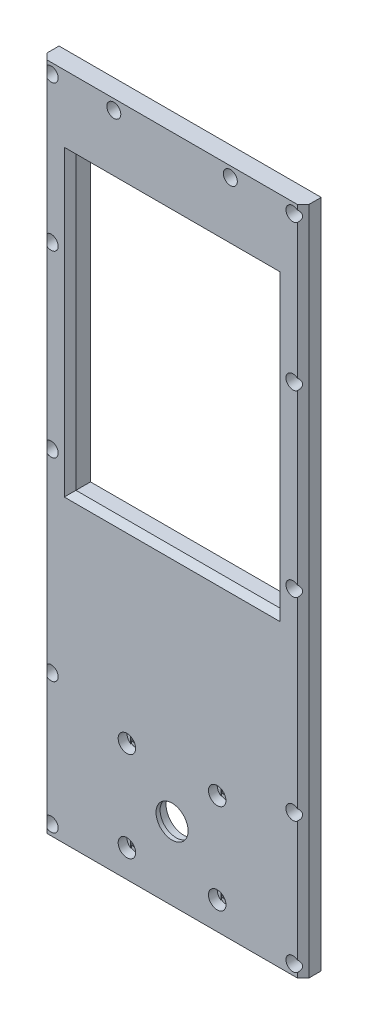
SolidWorks part; units mm, degrees
ref_plane "Front Plane" through (0, 0, 0) normal (0, 0, 1) x (1, 0, 0)
ref_plane "Top Plane" through (0, 0, 0) normal (0, 1, 0) x (1, 0, 0)
ref_plane "Right Plane" through (0, 0, 0) normal (1, 0, 0) x (0, 0, -1)
sketch "Sketch1" plane through (0, 0, 0) normal (0, 0, 1) x (1, 0, 0)
  line L1 (-45, -115) -> (45, -115)
  line L2 (-45, -115) -> (-45, 115)
  line L3 (-45, 115) -> (45, 115)
  line L4 (45, -115) -> (45, 115)
  line L5 (-45, -115) -> (45, 115) construction
  line L6 (-45, 115) -> (45, -115) construction
  line L7 (-38, -108) -> (38, -108)
  line L8 (-38, -108) -> (-38, 108)
  line L9 (-38, 108) -> (38, 108)
  line L10 (38, -108) -> (38, 108)
  line L11 (-38, -108) -> (38, 108) construction
  line L12 (-38, 108) -> (38, -108) construction
  point P0 (0, 0)
  point P6 (0, 0)
  dimension "D1" = 230
  dimension "D2" = 90
  dimension "D3" = 7
  dimension "D4" = 7
extrude "Boss-Extrude1" add sketch "Sketch1" along normal blind 7
sketch "Sketch2" plane through (0, 0, 7) normal (0, 0, 1) x (1, 0, 0)
  line L0 (38, -108) -> (38, 108) construction
  line L1 (-38, -108) -> (38, -108)
  line L2 (-38, -108) -> (-38, -58)
  line L3 (-38, -58) -> (38, -58)
  line L4 (38, -108) -> (38, -58)
  dimension "D1" = 50
extrude "Boss-Extrude2" add sketch "Sketch2" against normal up to surface (7 mm away) up to face at (0, 0, 0)
sketch "Sketch3" plane through (0, 0, 0) normal (0, 0, -1) x (-1, 0, 0)
  line L0 (0, -115) -> (0, -90) construction
  line L1 (45, -115) -> (-45, -115) construction
  circle A0 centre (0, -90) radius 5.5
  dimension "D1" = 11
  dimension "D2" = 25
extrude "Cut-Extrude1" cut sketch "Sketch3" against normal through all
sketch "Sketch4" plane through (0, 0, 0) normal (0, 0, -1) x (-1, 0, 0)
  circle A0 centre (0, -90) radius 6.05
  dimension "D1" = 12.1
extrude "Cut-Extrude2" cut sketch "Sketch4" against normal offset from surface (5.6 mm away) 1.4 up to face at (-5.5, -90, 7)
sketch "Sketch5" plane through (0, 0, 0) normal (0, 0, -1) x (-1, 0, 0)
  circle A0 centre (0, -90) radius 12
  dimension "D1" = 24
extrude "Cut-Extrude3" cut sketch "Sketch5" against normal offset from surface (3 mm away) 2.6 up to face at (-6.05, -90, 5.6)
sketch "Sketch6" plane through (0, 0, 0) normal (0, 0, -1) x (-1, 0, 0)
  line L1 (-15.5, -105.5) -> (15.5, -105.5) construction
  line L2 (-15.5, -105.5) -> (-15.5, -74.5) construction
  line L3 (-15.5, -74.5) -> (15.5, -74.5) construction
  line L4 (15.5, -105.5) -> (15.5, -74.5) construction
  line L5 (-15.5, -105.5) -> (15.5, -74.5) construction
  line L6 (-15.5, -74.5) -> (15.5, -105.5) construction
  circle A0 centre (-15.5, -74.5) radius 1.7
  circle A1 centre (15.5, -74.5) radius 1.7
  circle A2 centre (15.5, -105.5) radius 1.7
  circle A3 centre (-15.5, -105.5) radius 1.7
  point P0 (0, -90)
  dimension "D2" = 3.4
  dimension "D1" = 31
extrude "Cut-Extrude4" cut sketch "Sketch6" against normal through all
sketch "Sketch7" plane through (0, 0, 0) normal (0, 0, -1) x (-1, 0, 0)
  line L1 (-30, -112.5) -> (30, -112.5)
  line L2 (-30, -112.5) -> (-30, -67.5)
  line L3 (-30, -67.5) -> (30, -67.5)
  line L4 (30, -112.5) -> (30, -67.5)
  line L5 (-30, -112.5) -> (30, -67.5) construction
  line L6 (-30, -67.5) -> (30, -112.5) construction
  point P0 (0, -90)
  dimension "D1" = 60
  dimension "D2" = 45
extrude "Cut-Extrude5" cut sketch "Sketch7" against normal blind 1
sketch "Sketch8" plane through (0, 0, 7) normal (0, 0, 1) x (1, 0, 0)
  circle A0 centre (-15.5, -74.5) radius 3
  circle A1 centre (15.5, -74.5) radius 3
  circle A2 centre (15.5, -105.5) radius 3
  circle A3 centre (-15.5, -105.5) radius 3
  dimension "D1" = 6
extrude "Cut-Extrude6" cut sketch "Sketch8" against normal blind 3
sketch "Sketch9" plane through (0, 0, 7) normal (0, 0, 1) x (1, 0, 0)
  line L0 (-45, 115) -> (-45, -115) construction
  line L1 (-41.5, -111.5) -> (41.5, -111.5) construction
  line L2 (-41.5, -111.5) -> (-41.5, 111.5) construction
  line L3 (-41.5, 111.5) -> (41.5, 111.5) construction
  line L4 (41.5, -111.5) -> (41.5, 111.5) construction
  line L5 (-41.5, -111.5) -> (41.5, 111.5) construction
  line L6 (-41.5, 111.5) -> (41.5, -111.5) construction
  line L7 (45, 115) -> (-45, 115) construction
  circle A0 centre (-41.5, 111.5) radius 1.45
  circle A1 centre (41.5, 111.5) radius 1.45
  circle A4 centre (-41.5, -111.5) radius 1.45
  circle A5 centre (41.5, -111.5) radius 1.45
  circle A6 centre (-41.5, 61.5) radius 1.45
  circle A7 centre (41.5, 61.5) radius 1.45
  circle A8 centre (41.5, -66.5) radius 1.45
  circle A9 centre (-41.5, -66.5) radius 1.45
  circle A10 centre (-41.5, 0) radius 1.45
  circle A11 centre (41.5, 0) radius 1.45
  point P0 (0, 0)
  dimension "D3" = 2.9
  dimension "D1" = 3.5
  dimension "D2" = 3.5
  dimension "D4" = 45
  dimension "D5" = 50
extrude "Cut-Extrude7" cut sketch "Sketch9" against normal through all
sketch "Sketch10" plane through (0, 0, 7) normal (0, 0, 1) x (1, 0, 0)
  circle A0 centre (-41.5, 111.5) radius 2.4
  circle A1 centre (41.5, 61.5) radius 2.4
  circle A2 centre (-41.5, 61.5) radius 2.4
  circle A3 centre (41.5, 111.5) radius 2.4
  circle A4 centre (-41.5, -111.5) radius 2.4
  circle A5 centre (41.5, -111.5) radius 2.4
  circle A6 centre (-41.5, -66.5) radius 2.4
  circle A7 centre (41.5, -66.5) radius 2.4
  circle A8 centre (-41.5, 0) radius 2.4
  circle A9 centre (41.5, 0) radius 2.4
  dimension "D1" = 4.8
extrude "Cut-Extrude8" cut sketch "Sketch10" against normal blind 5
chamfer "Chamfer1" distance 2 angle 45 2 edges at (-45, 0, 7) (45, 0, 7)
sketch "Sketch11" plane through (0, 0, 7) normal (0, 0, 1) x (1, 0, 0)
  line L0 (38, -58) -> (38, 108) construction
  line L1 (-38, -58) -> (38, -58)
  line L2 (-38, -58) -> (-38, -36.4)
  line L3 (-38, -36.4) -> (38, -36.4)
  line L4 (38, -58) -> (38, -36.4)
  line L5 (-43, -115) -> (43, -115) construction
  dimension "D1" = 78.6
extrude "Boss-Extrude3" add sketch "Sketch11" against normal up to surface (7 mm away) up to face at (-40.05, 0, 0)
sketch "Sketch12" plane through (0, 0, 7) normal (0, 0, 1) x (1, 0, 0)
  line L0 (-41.5, 111.5) -> (41.5, 111.5) construction
  line L1 (-20, 111.5) -> (20, 111.5) construction
  circle A0 centre (-20, 111.5) radius 1.45
  circle A1 centre (20, 111.5) radius 1.45
  circle A2 centre (-41.5, 111.5) radius 1.45 construction
  point P7 (0, 111.5)
  dimension "D1" = 40
extrude "Cut-Extrude9" cut sketch "Sketch12" against normal through all
sketch "Sketch13" plane through (0, 0, 7) normal (0, 0, 1) x (1, 0, 0)
  circle A0 centre (-20, 111.5) radius 2.4
  circle A1 centre (20, 111.5) radius 2.4
  circle A2 centre (-41.5, 111.5) radius 2.4 construction
extrude "Cut-Extrude10" cut sketch "Sketch13" against normal up to surface (5 mm away) up to face at (-39.1, 111.5, 2)
chamfer "Chamfer2" distance 0.8 angle 45 12 edges at (0, -115, 0) (-45, 0, 0) (0, 115, 0) (45, 0, 0) (38, 35.8, 7) (0, 108, 7) (-38, 35.8, 7) (0, -36.4, 7) (-38, 35.8, 0) (0, 108, 0) (38, 35.8, 0) (0, -36.4, 0)
sketch "Sketch14" plane through (0, 0, 2) normal (0, 0, 1) x (1, 0, 0)
  line L2 (-42.95, -68.4125) -> (-42.95, -64.5875)
  line L4 (-40.05, -68.4125) -> (-40.05, -64.5875)
  line L5 (-42.95, -68.4125) -> (-40.05, -64.5875) construction
  line L6 (-42.95, -64.5875) -> (-40.05, -68.4125) construction
  line L14 (-42.95, -113.4125) -> (-42.95, -109.5875)
  line L16 (-40.05, -113.4125) -> (-40.05, -109.5875)
  line L17 (-42.95, -113.4125) -> (-40.05, -109.5875) construction
  line L18 (-42.95, -109.5875) -> (-40.05, -113.4125) construction
  line L26 (-42.95, 59.5875) -> (-42.95, 63.4125)
  line L28 (-40.05, 59.5875) -> (-40.05, 63.4125)
  line L29 (-42.95, 59.5875) -> (-40.05, 63.4125) construction
  line L30 (-42.95, 63.4125) -> (-40.05, 59.5875) construction
  line L32 (-21.45, 109.5875) -> (-21.45, 113.4125)
  line L34 (-18.55, 109.5875) -> (-18.55, 113.4125)
  line L35 (-21.45, 109.5875) -> (-18.55, 113.4125) construction
  line L36 (-21.45, 113.4125) -> (-18.55, 109.5875) construction
  line L38 (-42.95, 109.5875) -> (-42.95, 113.4125)
  line L40 (-40.05, 109.5875) -> (-40.05, 113.4125)
  line L41 (-42.95, 109.5875) -> (-40.05, 113.4125) construction
  line L42 (-42.95, 113.4125) -> (-40.05, 109.5875) construction
  arc A0 (-43, -68.3735) -> (-43, -64.6265) centre (-41.5, -66.5) ccw construction
  circle A2 centre (-41.5, -111.5) radius 2.4 construction
  circle A4 centre (-41.5, 61.5) radius 2.4 construction
  circle A5 centre (-20, 111.5) radius 2.4 construction
  circle A6 centre (-41.5, 111.5) radius 2.4 construction
  circle A7 centre (-41.5, 111.5) radius 1.45 construction
  circle A8 centre (-20, 111.5) radius 1.45 construction
  circle A9 centre (-41.5, 61.5) radius 1.45 construction
  circle A10 centre (-41.5, -66.5) radius 1.45 construction
  circle A12 centre (-41.5, -111.5) radius 1.45 construction
  arc A16 (-21.45, 109.5875) -> (-18.55, 109.5875) centre (-20, 111.5) ccw
  arc A17 (-40.05, 113.4125) -> (-42.95, 113.4125) centre (-41.5, 111.5) ccw
  arc A18 (-40.05, 63.4125) -> (-42.95, 63.4125) centre (-41.5, 61.5) ccw
  arc A20 (-42.95, -68.4125) -> (-40.05, -68.4125) centre (-41.5, -66.5) ccw
  arc A22 (-40.05, -109.5875) -> (-42.95, -109.5875) centre (-41.5, -111.5) ccw
  arc A23 (-42.95, 109.5875) -> (-40.05, 109.5875) centre (-41.5, 111.5) ccw
  arc A24 (-18.55, 113.4125) -> (-21.45, 113.4125) centre (-20, 111.5) ccw
  arc A25 (-42.95, 59.5875) -> (-40.05, 59.5875) centre (-41.5, 61.5) ccw
  arc A26 (-40.05, -64.5875) -> (-42.95, -64.5875) centre (-41.5, -66.5) ccw
  arc A29 (-42.95, -113.4125) -> (-40.05, -113.4125) centre (-41.5, -111.5) ccw
  point P0 (-41.5, -66.5)
  point P17 (-41.5, -111.5)
  point P33 (-41.5, 61.5)
  point P41 (-20, 111.5)
  point P49 (-41.5, 111.5)
extrude "Cut-Extrude11" cut sketch "Sketch14" against normal blind 0.2
sketch "Sketch15" plane through (0, 0, 1.8) normal (0, 0, 1) x (1, 0, 0)
  line L0 (-40.05, -111.5) -> (-40.05, -109.5875) construction
  line L1 (-42.95, -112.95) -> (-40.05, -112.95)
  line L2 (-42.95, -112.95) -> (-42.95, -110.05)
  line L3 (-42.95, -110.05) -> (-40.05, -110.05)
  line L4 (-40.05, -112.95) -> (-40.05, -110.05)
  line L5 (-42.95, -112.95) -> (-40.05, -110.05) construction
  line L6 (-42.95, -110.05) -> (-40.05, -112.95) construction
  line L7 (-40.05, 61.5) -> (-40.05, 63.4125) construction
  line L8 (-42.95, -67.95) -> (-40.05, -67.95)
  line L9 (-42.95, -67.95) -> (-42.95, -65.05)
  line L10 (-42.95, -65.05) -> (-40.05, -65.05)
  line L11 (-40.05, -67.95) -> (-40.05, -65.05)
  line L12 (-42.95, -67.95) -> (-40.05, -65.05) construction
  line L13 (-42.95, -65.05) -> (-40.05, -67.95) construction
  line L14 (-42.95, 60.05) -> (-40.05, 60.05)
  line L15 (-42.95, 60.05) -> (-42.95, 62.95)
  line L16 (-42.95, 62.95) -> (-40.05, 62.95)
  line L17 (-40.05, 60.05) -> (-40.05, 62.95)
  line L18 (-42.95, 60.05) -> (-40.05, 62.95) construction
  line L19 (-42.95, 62.95) -> (-40.05, 60.05) construction
  line L20 (-40.05, 109.5875) -> (-40.05, 113.4125) construction
  line L21 (-42.95, 110.05) -> (-40.05, 110.05)
  line L22 (-42.95, 110.05) -> (-42.95, 112.95)
  line L23 (-42.95, 112.95) -> (-40.05, 112.95)
  line L24 (-40.05, 110.05) -> (-40.05, 112.95)
  line L25 (-42.95, 110.05) -> (-40.05, 112.95) construction
  line L26 (-42.95, 112.95) -> (-40.05, 110.05) construction
  line L27 (-18.55, 109.5875) -> (-18.55, 113.4125) construction
  line L28 (-21.45, 110.05) -> (-18.55, 110.05)
  line L29 (-21.45, 110.05) -> (-21.45, 112.95)
  line L30 (-21.45, 112.95) -> (-18.55, 112.95)
  line L31 (-18.55, 110.05) -> (-18.55, 112.95)
  line L32 (-21.45, 110.05) -> (-18.55, 112.95) construction
  line L33 (-21.45, 112.95) -> (-18.55, 110.05) construction
  arc A0 (-40.05, -66.5) -> (-42.95, -66.5) centre (-41.5, -66.5) ccw construction
  arc A1 (-40.05, 61.5) -> (-42.95, 61.5) centre (-41.5, 61.5) ccw construction
  arc A2 (-18.55, 111.5) -> (-21.45, 111.5) centre (-20, 111.5) ccw construction
  arc A3 (-40.05, 111.5) -> (-42.95, 111.5) centre (-41.5, 111.5) ccw construction
  point P0 (-41.5, -111.5)
  point P8 (-41.5, -66.5)
  point P17 (-41.5, 61.5)
  point P28 (-41.5, 111.5)
  point P36 (-20, 111.5)
extrude "Cut-Extrude12" cut sketch "Sketch15" against normal blind 0.2
sketch "Sketch16" plane through (0, 0, 4) normal (0, 0, 1) x (1, 0, 0)
  line L2 (-17.2, -76.9718) -> (-17.2, -72.0282)
  line L4 (-13.8, -76.9718) -> (-13.8, -72.0282)
  line L5 (-17.2, -76.9718) -> (-13.8, -72.0282) construction
  line L6 (-17.2, -72.0282) -> (-13.8, -76.9718) construction
  line L8 (-17.2, -107.9718) -> (-17.2, -103.0282)
  line L10 (-13.8, -107.9718) -> (-13.8, -103.0282)
  line L11 (-17.2, -107.9718) -> (-13.8, -103.0282) construction
  line L12 (-17.2, -103.0282) -> (-13.8, -107.9718) construction
  circle A0 centre (-15.5, -74.5) radius 3 construction
  circle A1 centre (-15.5, -105.5) radius 3 construction
  circle A2 centre (-15.5, -105.5) radius 1.7 construction
  circle A3 centre (-15.5, -74.5) radius 1.7 construction
  circle A4 centre (-15.5, -105.5) radius 3 construction
  circle A5 centre (-15.5, -74.5) radius 3 construction
  arc A6 (-13.8, -103.0282) -> (-17.2, -103.0282) centre (-15.5, -105.5) ccw
  arc A7 (-17.2, -76.9718) -> (-13.8, -76.9718) centre (-15.5, -74.5) ccw
  arc A8 (-13.8, -72.0282) -> (-17.2, -72.0282) centre (-15.5, -74.5) ccw
  arc A9 (-17.2, -107.9718) -> (-13.8, -107.9718) centre (-15.5, -105.5) ccw
  point P0 (-15.5, -74.5)
  point P8 (-15.5, -105.5)
extrude "Cut-Extrude13" cut sketch "Sketch16" against normal blind 0.2
sketch "Sketch17" plane through (0, 0, 3.8) normal (0, 0, 1) x (1, 0, 0)
  line L0 (-13.8, -76.9718) -> (-13.8, -72.0282) construction
  line L1 (-17.2, -76.2) -> (-13.8, -76.2)
  line L2 (-17.2, -76.2) -> (-17.2, -72.8)
  line L3 (-17.2, -72.8) -> (-13.8, -72.8)
  line L4 (-13.8, -76.2) -> (-13.8, -72.8)
  line L5 (-17.2, -76.2) -> (-13.8, -72.8) construction
  line L6 (-17.2, -72.8) -> (-13.8, -76.2) construction
  line L7 (-13.8, -107.9718) -> (-13.8, -103.0282) construction
  line L8 (-17.2, -107.2) -> (-13.8, -107.2)
  line L9 (-17.2, -107.2) -> (-17.2, -103.8)
  line L10 (-17.2, -103.8) -> (-13.8, -103.8)
  line L11 (-13.8, -107.2) -> (-13.8, -103.8)
  line L12 (-17.2, -107.2) -> (-13.8, -103.8) construction
  line L13 (-17.2, -103.8) -> (-13.8, -107.2) construction
  arc A0 (-13.8, -105.5) -> (-17.2, -105.5) centre (-15.5, -105.5) ccw construction
  arc A1 (-13.8, -74.5) -> (-17.2, -74.5) centre (-15.5, -74.5) ccw construction
  point P0 (-15.5, -74.5)
  point P8 (-15.5, -105.5)
extrude "Cut-Extrude14" cut sketch "Sketch17" against normal blind 0.2
mirror "Mirror1" about plane through (0, 0, 0) normal (1, 0, 0) of "Cut-Extrude12", "Cut-Extrude13", "Cut-Extrude14", "Cut-Extrude11"
sketch "Sketch18" plane through (0, 0, 7) normal (0, 0, 1) x (1, 0, 0)
  line L0 (38.8, 108.8) -> (38.8, -37.2) construction
  line L1 (-38.8, 108.8) -> (38.8, 108.8)
  line L2 (-38.8, 108.8) -> (-38.8, 70.8)
  line L3 (-38.8, 70.8) -> (38.8, 70.8)
  line L4 (38.8, 108.8) -> (38.8, 70.8)
  dimension "D1" = 38
extrude "Boss-Extrude4" add sketch "Sketch18" against normal up to surface (7 mm away) up to face at (0, 35.8, 0)
chamfer "Chamfer3" distance 0.8 angle 45 1 edges at (0, 70.8, 7)
sketch "Sketch19" plane through (0, 0, 7) normal (0, 0, 1) x (1, 0, 0)
  line L1 (-38.8, 71.6) -> (38.8, 71.6)
  line L2 (-38.8, 71.6) -> (-38.8, -37.2)
  line L3 (-38.8, -37.2) -> (38.8, -37.2)
  line L4 (38.8, 71.6) -> (38.8, -37.2)
extrude "Boss-Extrude5" add sketch "Sketch19" against normal up to surface (7 mm away) up to face at (0, 16.8, 0)
sketch "Sketch20" plane through (0, 0, 2) normal (0, 0, 1) x (1, 0, 0)
  line L2 (-42.95, -1.9125) -> (-42.95, 1.9125)
  line L4 (-40.05, -1.9125) -> (-40.05, 1.9125)
  line L5 (-42.95, -1.9125) -> (-40.05, 1.9125) construction
  line L6 (-42.95, 1.9125) -> (-40.05, -1.9125) construction
  arc A0 (-43, -1.8735) -> (-43, 1.8735) centre (-41.5, 0) ccw construction
  circle A1 centre (-41.5, 0) radius 1.45 construction
  arc A2 (-42.95, -1.9125) -> (-40.05, -1.9125) centre (-41.5, 0) ccw
  arc A3 (-40.05, 1.9125) -> (-42.95, 1.9125) centre (-41.5, 0) ccw
  point P0 (-41.5, 0)
extrude "Cut-Extrude15" cut sketch "Sketch20" against normal blind 0.2
sketch "Sketch21" plane through (0, 0, 1.8) normal (0, 0, 1) x (1, 0, 0)
  line L0 (-40.05, -1.9125) -> (-40.05, 1.9125) construction
  line L1 (-42.95, -1.45) -> (-40.05, -1.45)
  line L2 (-42.95, -1.45) -> (-42.95, 1.45)
  line L3 (-42.95, 1.45) -> (-40.05, 1.45)
  line L4 (-40.05, -1.45) -> (-40.05, 1.45)
  line L5 (-42.95, -1.45) -> (-40.05, 1.45) construction
  line L6 (-42.95, 1.45) -> (-40.05, -1.45) construction
  arc A0 (-40.05, 0) -> (-42.95, 0) centre (-41.5, 0) ccw construction
  point P0 (-41.5, 0)
extrude "Cut-Extrude16" cut sketch "Sketch21" against normal blind 0.2
mirror "Mirror2" about plane through (0, 0, 0) normal (1, 0, 0) of "Cut-Extrude16", "Cut-Extrude15"
sketch "Sketch22" plane through (0, 0, 7) normal (0, 0, 1) x (1, 0, 0)
  line L0 (-43, -115) -> (43, -115) construction
  line L1 (-35, -10) -> (35, -10)
  line L2 (-35, -10) -> (-35, 90)
  line L3 (-35, 90) -> (35, 90)
  line L4 (35, -10) -> (35, 90)
  line L5 (-35, -10) -> (35, 90) construction
  line L6 (-35, 90) -> (35, -10) construction
  point P0 (0, 40)
  dimension "D1" = 70
  dimension "D2" = 100
  dimension "D3" = 155
extrude "Cut-Extrude17" cut sketch "Sketch22" against normal through all
chamfer "Chamfer4" distance 2 angle 45 4 edges at (-35, 40, 7) (0, -10, 7) (35, 40, 7) (0, 90, 7)
